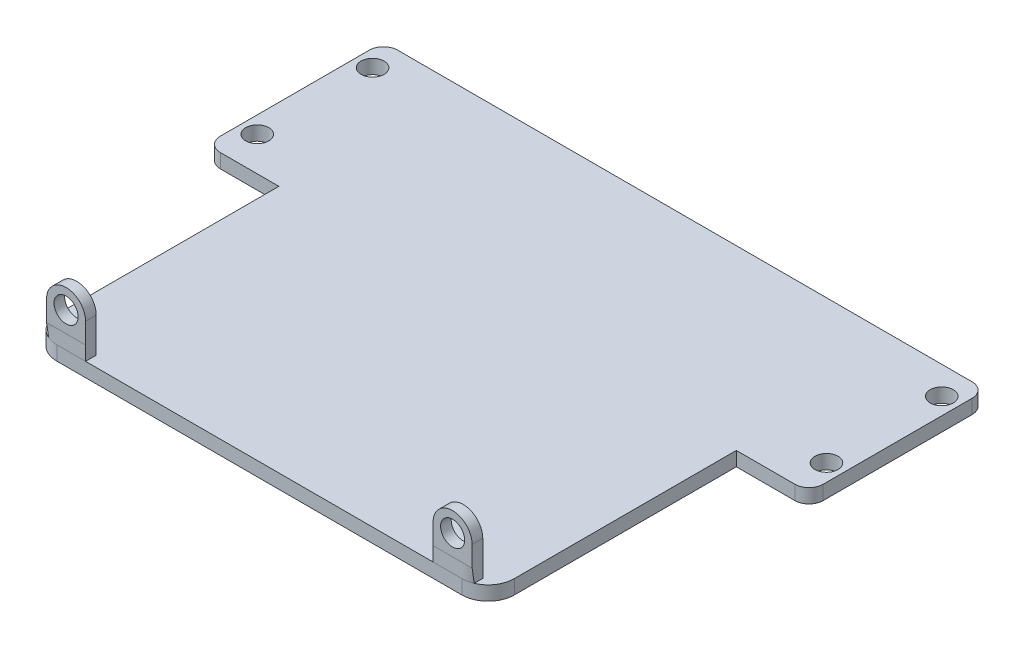
SolidWorks part; units mm, degrees
ref_plane "前视基准面" through (0, 0, 0) normal (0, 0, 1) x (1, 0, 0)
ref_plane "上视基准面" through (0, 0, 0) normal (0, 1, 0) x (1, 0, 0)
ref_plane "右视基准面" through (0, 0, 0) normal (1, 0, 0) x (0, 0, -1)
sketch "草图1" plane through (0, 0, 0) normal (0, 1, 0) x (1, 0, 0)
  line L0 (-15, -259.0169) -> (-15, 12805.6838) construction
  line L1 (15, -261.2731) -> (15, 12803.4276) construction
  line L2 (0, -1000) -> (0, 49000) construction
  line L3 (-1006.7233, 60) -> (48993.2767, 60) construction
  line L4 (-1005.83, 0) -> (48994.17, 0) construction
  line L5 (-1015, 1.7) -> (48985, 1.7) construction
  line L6 (-1015, 58.3) -> (48985, 58.3) construction
  line L7 (-32.25, -984.2827) -> (-32.25, 49015.7173) construction
  line L8 (32.25, -985.1) -> (32.25, 49014.9) construction
  line L9 (-28.55, 62) -> (28.55, 62)
  line L10 (32.25, 58.3) -> (32.25, 1.7)
  line L11 (28.55, -2) -> (-28.55, -2)
  line L12 (-32.25, 1.7) -> (-32.25, 58.3)
  arc A5 (-32.25, 1.7) -> (-28.55, -2) centre (-28.55, 1.7) ccw
  arc A6 (32.25, 1.7) -> (28.55, -2) centre (28.55, 1.7) cw
  arc A7 (28.55, 62) -> (32.25, 58.3) centre (28.55, 58.3) cw
  arc A8 (-28.55, 62) -> (-32.25, 58.3) centre (-28.55, 58.3) ccw
  dimension "D4" = 56.6
  dimension "D8" = 64.5
  dimension "D1" = 30
  dimension "D2" = 15
  dimension "D3" = 60
  dimension "D9" = 32.25
extrude "凸台-拉伸2" add sketch "草图1" against normal blind 2
sketch "草图4" plane through (0, 0, 0) normal (0, 1, 0) x (1, 0, 0)
  line L0 (-25.5, -990.3861) -> (-25.5, 49009.6139) construction
  line L1 (25.5, -991.9534) -> (25.5, 49008.0466) construction
  line L2 (-29, -982.9974) -> (-29, 49017.0026) construction
  line L3 (29, -984.9677) -> (29, 49015.0323) construction
  line L4 (0, -1000) -> (0, 49000) construction
  line L8 (-28.55, -2) -> (28.55, -2) construction
  line L14 (-30, -998.5041) -> (-30, 49001.4959) construction
  line L15 (-24.5, -999.0098) -> (-24.5, 49000.9902) construction
  line L17 (-30, -0.5) -> (-30, -1.704)
  line L18 (-30, -0.5) -> (-24.5, -0.5)
  line L19 (-24.5, -0.5) -> (-24.5, -2)
  line L20 (-28.55, -2) -> (-24.5, -2)
  arc A2 (-28.55, -2) -> (-30, -1.704) centre (-28.55, 1.7) cw
  dimension "D6" = 1
  dimension "D1" = 51
  dimension "D2" = 58
  dimension "D3" = 29
  dimension "D4" = 25.5
  dimension "D7" = 1
ref_plane "基准面4" through (0, 2, 0) normal (0, 1, 0) x (1, 0, 0)
sketch "草图5" plane through (0, 2, 0) normal (0, 1, 0) x (1, 0, 0)
  line L6 (-30, -200998.5041) -> (-30, 249001.4959) construction
  line L7 (-30, -2) -> (-30, -0.5)
  line L8 (-30, -0.5) -> (-24.5, -0.5)
  line L9 (-24.5, -0.5) -> (-24.5, -2)
  line L11 (-24.5, -2) -> (-28.55, -2)
  line L12 (-28.55, -2) -> (-30, -2)
loft "放样4" add profiles "草图4", "草图5" connector at (-24.5, 0, 2) connector at (-24.5, 2, 2)
sketch "草图6" plane through (0, 0, 0) normal (0, 0, 1) x (1, 0, 0)
  line L0 (-1028.1213, 3.2) -> (48971.8787, 3.2) construction
  line L1 (-24.5, 0) -> (28.55, 0) construction
  line L2 (-1026.7035, 6.6) -> (48973.2965, 6.6) construction
  line L3 (-24.5, 4.9) -> (-24.5, 2)
  line L4 (-24.5, 2) -> (-24.5, 0) construction
  line L5 (-30, 2) -> (-30, 4.9)
  line L6 (35.475, 2) -> (-35.475, 2) construction
  line L7 (-30, 0) -> (-30, 2) construction
  line L8 (-30, 2) -> (-24.5, 2)
  circle A0 centre (-27.25, 4.9) radius 1.7
  arc A1 (-24.5, 4.9) -> (-30, 4.9) centre (-27.25, 4.9) ccw
  dimension "D3" = 2.75
  dimension "D1" = 3.2
  dimension "D2" = 3.4
extrude "凸台-拉伸3" add sketch "草图6" along normal blind 1.5 from offset 0.5
mirror "镜向1" about plane through (0, 0, 0) normal (1, 0, 0) of "放样4", "凸台-拉伸3"
sketch "草图7" plane through (0, 0, 0) normal (0, 1, 0) x (1, 0, 0)
  line L0 (-42.5, 58) -> (42.5, 58)
  line L1 (42.5, 58) -> (42.5, 33)
  line L2 (42.5, 33) -> (-42.5, 33)
  line L3 (-42.5, 33) -> (-42.5, 58)
  line L4 (28.55, 62) -> (-28.55, 62) construction
  line L5 (0, 62) -> (0, 58) construction
  dimension "D1" = 85
  dimension "D2" = 42.5
  dimension "D3" = 4
  dimension "D4" = 25
extrude "凸台-拉伸4" add sketch "草图7" against normal blind 2
fillet "圆角2" radius 10 1 edges at (-32.25, -1, -58)
fillet "圆角4" radius 10 1 edges at (32.25, -1, -58)
sketch "草图8" plane through (0, 0, 0) normal (0, 1, 0) x (1, 0, 0)
  line L0 (-40.125, 54.085) -> (40.125, 54.085) construction
  line L1 (28.55, 62) -> (-28.55, 62) construction
  line L2 (0, 62) -> (0, 54.085) construction
  line L3 (-40.125, 54.085) -> (-40.125, 37.835) construction
  line L4 (-40.125, 37.835) -> (40.125, 37.835) construction
  line L5 (40.125, 37.835) -> (40.125, 54.085) construction
  circle A0 centre (-40.125, 54.085) radius 1.625
  circle A1 centre (40.125, 54.085) radius 1.625
  circle A2 centre (40.125, 37.835) radius 1.625
  circle A3 centre (-40.125, 37.835) radius 1.625
  dimension "D1" = 3.25
  dimension "D2" = 3.25
  dimension "D3" = 3.25
  dimension "D4" = 3.25
  dimension "D5" = 80.25
  dimension "D6" = 40.125
  dimension "D7" = 16.25
extrude "切除-拉伸1" cut sketch "草图8" against normal blind 2
fillet "圆角6" radius 2 1 edges at (-42.5, -1, -58)
fillet "圆角7" radius 2 1 edges at (42.5, -1, -58)
sketch "草图9" plane through (0, 0, 0) normal (0, 1, 0) x (1, 0, 0)
  line L0 (-38.2247, 58) -> (-40.5, 58) construction
  line L1 (-51.2589, 67.4647) -> (50.0267, 67.4647)
  line L2 (-51.2589, 67.4647) -> (-51.2589, 58)
  line L3 (-51.2589, 58) -> (50.0267, 58)
  line L4 (50.0267, 67.4647) -> (50.0267, 58)
extrude "切除-拉伸2" cut sketch "草图9" against normal blind 2
fillet "圆角8" radius 2 1 edges at (-42.5, -1, -33)
fillet "圆角9" radius 2 1 edges at (42.5, -1, -33)
